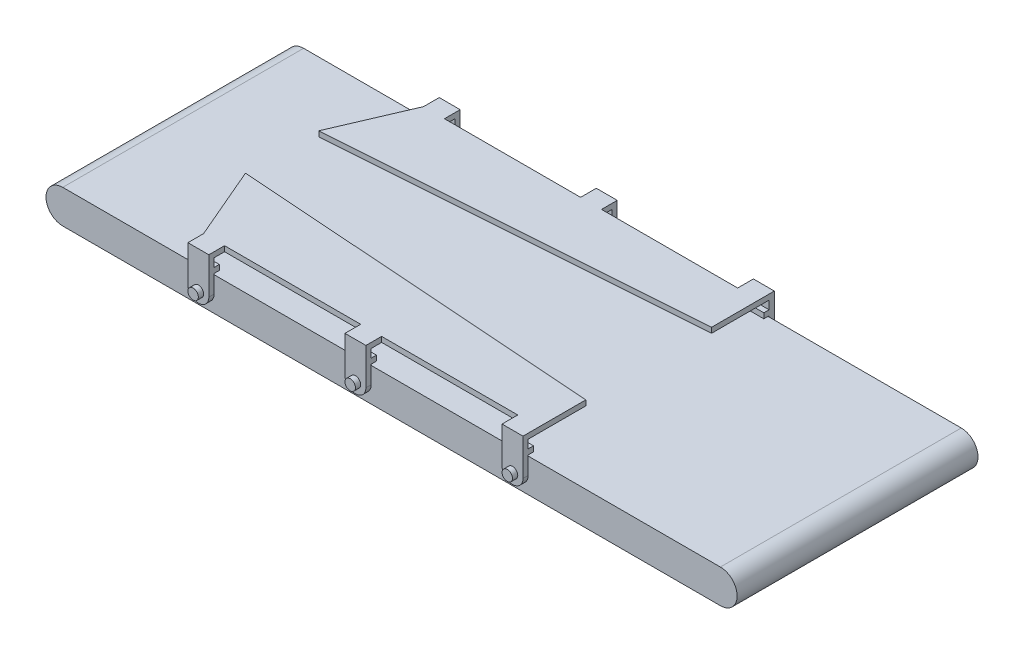
SolidWorks part; units mm, degrees
ref_plane "Front Plane" through (0, 0, 0) normal (0, 0, 1) x (1, 0, 0)
ref_plane "Top Plane" through (0, 0, 0) normal (0, 1, 0) x (1, 0, 0)
ref_plane "Right Plane" through (0, 0, 0) normal (1, 0, 0) x (0, 0, -1)
sketch "Esboço1" plane through (0, 0, 0) normal (0, 1, 0) x (1, 0, 0)
  line L1 (0, 0) -> (660, 0)
  line L2 (0, 0) -> (0, 230)
  line L3 (0, 230) -> (660, 230)
  line L4 (660, 0) -> (660, 230)
  dimension "D1" = 660
  dimension "D2" = 230
extrude "Ressalto-extrusão1" add sketch "Esboço1" along normal blind 32
fillet "Filete1" 2 edges at (0, 32, -115) (0, 0, -115) type full round first side face at (330, 32, -115) second side face at (330, 0, -115) middle face at (0, 16, -115)
fillet "Filete2" 2 edges at (660, 32, -115) (660, 0, -115) type full round first side face at (338, 32, -115) second side face at (338, 0, -115) middle face at (660, 16, -115)
ref_plane "Plano1" through (0, 0, -115) normal (0, 0, 1) x (1, 0, 0)
sketch "Esboço2" plane through (0, 0, 0) normal (0, 0, 1) x (1, 0, 0)
  line L0 (16, 32) -> (644, 32) construction
  circle A0 centre (150.5, 16) radius 5
  arc A1 (16, 32) -> (16, 0) centre (16, 16) ccw construction
  point P5 (0, 16)
  dimension "D2" = 10
  dimension "D1" = 150.5
  dimension "D3" = 16
extrude "Ressalto-extrusão2" add sketch "Esboço2" along normal blind 10
mirror "Espelhar1" about plane through (0, 0, -115) normal (0, 0, 1) of "Ressalto-extrusão2"
pattern_linear "Padrão linear1" count 3 spacing 150 along (1, 0, 0) of "Ressalto-extrusão2", "Espelhar1"
sketch "Esboço6" plane through (0, 0, 0) normal (0, 0, 1) x (1, 0, 0)
  line L0 (140.5, 16) -> (140.5, 46)
  line L1 (140.5, 46) -> (160.5, 46)
  line L2 (160.5, 46) -> (160.5, 16)
  circle A0 centre (150.5, 16) radius 5 construction
  circle A1 centre (150.5, 16) radius 5
  arc A2 (140.5, 16) -> (160.5, 16) centre (150.5, 16) ccw
  dimension "D1" = 10
  dimension "D2" = 30
extrude "Ressalto-extrusão7" add sketch "Esboço6" along normal blind 5
sketch "Esboço10" plane through (0, 0, 0) normal (0, 0, -1) x (-1, 0, 0)
  line L0 (-140.5, 46) -> (-140.5, 32) construction
  line L1 (-140.5, 33) -> (-160.5, 33)
  line L2 (-140.5, 33) -> (-140.5, 38)
  line L3 (-140.5, 38) -> (-160.5, 38)
  line L4 (-160.5, 33) -> (-160.5, 38)
  line L5 (-160.5, 32) -> (-160.5, 46) construction
  line L6 (-160.5, 32) -> (-140.5, 32) construction
  dimension "D1" = 5
  dimension "D2" = 1
extrude "Ressalto-extrusão11" add sketch "Esboço10" along normal blind 5
pattern_linear "Padrão linear2" count 3 spacing 150 along (1, 0, 0) of "Ressalto-extrusão7", "Ressalto-extrusão11"
sketch "Esboço9" plane through (0, 46, 0) normal (0, 1, 0) x (1, 0, 0)
  line L0 (160.5, -5) -> (160.5, 10)
  line L1 (160.5, -5) -> (140.5, -5)
  line L2 (140.5, -5) -> (140.5, 10)
  line L4 (310.5, -5) -> (290.5, -5)
  line L5 (290.5, -5) -> (290.5, 10)
  line L6 (290.5, 10) -> (160.5, 10)
  line L7 (140.5, 10) -> (110.5, 80)
  line L8 (110.5, 80) -> (460.5, 55)
  line L9 (440.5, -5) -> (440.5, 10)
  line L10 (440.5, 10) -> (310.5, 10)
  line L11 (310.5, 10) -> (310.5, -5)
  line L12 (460.5, -5) -> (460.5, 55)
  line L13 (460.5, -5) -> (440.5, -5)
  dimension "D1" = 45
  dimension "D2" = 70
  dimension "D3" = 15
  dimension "D4" = 30
extrude "Ressalto-extrusão10" add sketch "Esboço9" along normal blind 5
ref_plane "Plano2" through (0, 0, -115) normal (0, 0, -1) x (-1, 0, 0)
mirror "Espelhar2" about plane through (0, 0, -115) normal (0, 0, -1) of "Padrão linear2", "Ressalto-extrusão7", "Ressalto-extrusão10"
